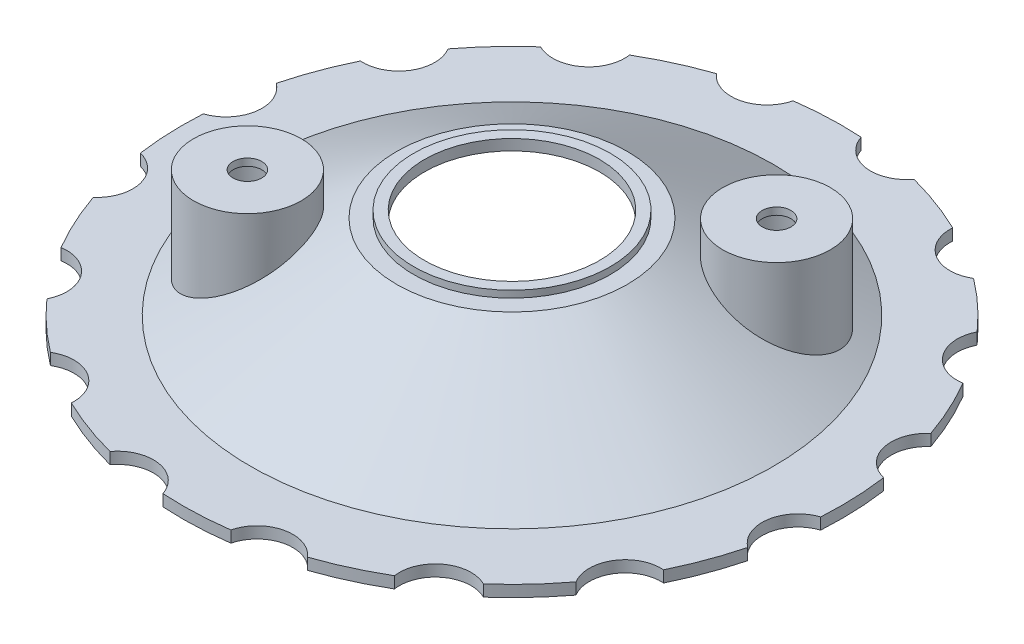
SolidWorks part; units mm, degrees
note: The reader was unsure of these and kept them because the rebuilt part matched: shared geometry of "Sketch4<6>", "Sketch3<4>", "Sketch4<8>", "Sketch4<10>", "Sketch4<11>".
ref_plane "Front Plane" through (0, 0, 0) normal (0, 0, 1) x (1, 0, 0)
ref_plane "Top Plane" through (0, 0, 0) normal (0, 1, 0) x (1, 0, 0)
ref_plane "Right Plane" through (0, 0, 0) normal (1, 0, 0) x (0, 0, -1)
sketch "Sketch3" plane through (0, 0, 0) normal (0, 0, 1) x (1, 0, 0)
  line L0 (0, 0) -> (0, 8)
  line L1 (0, 8) -> (6.1, 8)
  line L2 (6.1, 8) -> (19.9564, 0)
  line L3 (19.9564, 0) -> (6.1, 0)
  line L4 (6.1, 0) -> (0, 0)
  line L5 (19.9564, 1.3856) -> (8.0323, 8.27)
  line L6 (19.9564, 0) -> (19.9564, 1.3856)
  line L7 (6.85, 8.75) -> (6.85, 8.27)
  line L8 (6.1, 8) -> (6.1, 8.75)
  line L9 (6.1, 8.75) -> (6.85, 8.75)
  line L10 (6.85, 8.27) -> (8.0323, 8.27)
  line L11 (22.9564, 0) -> (22.9564, 2.39)
  line L12 (22.9564, 2.39) -> (15.8168, 2.39)
  line L13 (22.9564, 0) -> (19.9564, 0)
  dimension "D1" = 19.9564
  dimension "D2" = 60
  dimension "D3" = 8
  dimension "D4" = 0.75
  dimension "D5" = 0.48
  dimension "D6" = 0.75
  dimension "D7" = 6.1
  dimension "D8" = 1.2
  dimension "D9" = 2.39
  dimension "D10" = 1.3856
  dimension "D11" = 22.9564
ref_axis "Axis1" through (0, 0, 0) along (0, 1, 0)
revolve "Revolve1" add sketch "Sketch3" angle 360 about axis through (0, 0, 0) along (0, 1, 0)
sketch "Sketch4" plane through (0, 0, 0) normal (0, 1, 0) x (1, 0, 0)
  line L0 (118.8917, 681.3815) -> (968.8917, 681.3815) construction
  line L1 (-10.6926, -7.74) -> (10.6926, 7.74)
  line L5 (31.7232, 27.4788) -> (0, 0)
  line L6 (0, 0) -> (-32.7711, 26.633)
  line L7 (0.7496, -47.7541) -> (0, 0)
  line L8 (0, 0) -> (-24, -0.3767)
  line L9 (0, 0) -> (-19.4317, -14.0857)
  circle A1 centre (-32.7711, 26.633) radius 1.7004
  circle A2 centre (0.7496, -47.7541) radius 1.6902
  circle A3 centre (31.7232, 27.4788) radius 1.7049
  circle A4 centre (0, 0) radius 13.2
  circle A5 centre (0, 0) radius 19.96
  circle A6 centre (-10.6926, -7.74) radius 2.25
  circle A7 centre (10.6926, 7.74) radius 2.25
  circle A8 centre (10.6926, 7.74) radius 3.75
  circle A9 centre (-10.6926, -7.74) radius 3.75
  circle A26 centre (-19.4317, -14.0857) radius 2.5
  circle A27 centre (-23.343, -5.5773) radius 2.5
  circle A28 centre (-23.7004, 3.7802) radius 2.5
  circle A29 centre (-20.4497, 12.5622) radius 2.5
  circle A30 centre (-14.0857, 19.4317) radius 2.5
  circle A31 centre (-5.5773, 23.343) radius 2.5
  circle A32 centre (3.7802, 23.7004) radius 2.5
  circle A33 centre (12.5622, 20.4497) radius 2.5
  circle A34 centre (19.4317, 14.0857) radius 2.5
  circle A35 centre (23.343, 5.5773) radius 2.5
  circle A36 centre (23.7004, -3.7802) radius 2.5
  circle A37 centre (20.4497, -12.5622) radius 2.5
  circle A38 centre (14.0857, -19.4317) radius 2.5
  circle A39 centre (5.5773, -23.343) radius 2.5
  circle A40 centre (-3.7802, -23.7004) radius 2.5
  circle A41 centre (-12.5622, -20.4497) radius 2.5
  spline S1 degree 3 poles (43.8735, -26.7609) (31.5074, -48.7539) (7.0538, -66.6063) (-36.5969, -52.4475) (-49.7377, -17.6551) (-51.9696, 4.1899) (-49.3092, 25.911) (-32.1878, 46.9787) (-4.6171, 56.277) (26.6667, 51.503) (51.4432, 21.9878) (49.0137, -13.034) (43.8735, -26.7609) (31.5074, -48.7539) (7.0538, -66.6063) knots -0.186216 -0.081166 -0.008117 0 0.104424 0.202069 0.320062 0.340993 0.411384 0.528959 0.5813 0.689189 0.813784 0.918834 0.991883 1 1.104424 1.202069 1.320062 only from (37.8954, -37.3216) to (37.8954, -37.3216)
  point P61 (0, 0)
  dimension "D5" = 7.5
  dimension "D6" = 4.5
  dimension "D7" = 4.5
  dimension "D8" = 7.5
  dimension "D9" = 26.4
  dimension "D11" = 24
  dimension "D14" = 16
  dimension "D12" = 5
  dimension "D1" = 130
  dimension "D2" = 130
  dimension "D3" = 42.2287
  dimension "D4" = 41.9696
  dimension "D10" = 24
  dimension "D13" = 55
extrude "Boss-Extrude1" add sketch "Sketch4" along normal blind 1
extrude "Boss-Extrude2" add sketch "Sketch4<6>" along direction (0, 1, 0) on the side of the normal blind 9.2 contours L1 A9 A4 A6 | A4 A9 L1 A6 | A4 A8 L5 A7 | L5 A8 A4 A7 | A4 A8 L5 A7 | L5 A8 L1 A7 | L1 A8 A4 A7 | A4 A9 L9 A6 | L9 A9 A4 A6 | A4 A9 L9 A6
sketch "Sketch4<6>" plane through (0, 0, 0) normal (0, 1, 0) x (1, 0, 0) same geometry as "Sketch4"
revolve "Cut-Revolve1" cut sketch "Sketch3<4>" angle 360 about axis through (0, 0, 0) along (0, 1, 0)
sketch "Sketch3<4>" plane through (0, 0, 0) normal (0, 0, 1) x (1, 0, 0) same geometry as "Sketch3"
ref_plane "Plane3" through (0, 9.2, 0) normal (0, 1, 0) x (1, 0, 0)
sketch "Sketch6" plane through (0, 9.2, 0) normal (0, 1, 0) x (1, 0, 0)
  line L0 (0, 0) -> (-10.6926, -7.74)
  line L5 (0, 0) -> (10.6926, 7.74)
  circle A5 centre (-10.6926, -7.74) radius 1
  circle A6 centre (-10.6926, -7.74) radius 3.75
  circle A9 centre (10.6926, 7.74) radius 1
  circle A10 centre (10.6926, 7.74) radius 3.75
  point P7 (-0.0007, 0)
  dimension "D1" = 2
  dimension "D2" = 7.5
  dimension "D3" = 2
extrude "Boss-Extrude10" add sketch "Sketch6" along normal blind 0.5
extrude "Cut-Extrude1" cut sketch "Sketch4<8>" along normal blind 8 contours A6 | A7
sketch "Sketch4<8>" plane through (0, 0, 0) normal (0, 1, 0) x (1, 0, 0) same geometry as "Sketch4"
extrude "Cut-Extrude3" cut sketch "Sketch4<10>" along normal blind 1.59 contours S1
sketch "Sketch4<10>" plane through (0, 0, 0) normal (0, 1, 0) x (1, 0, 0) same geometry as "Sketch4"
extrude "Cut-Extrude4" cut sketch "Sketch4<11>" along normal blind 30
sketch "Sketch4<11>" plane through (0, 0, 0) normal (0, 1, 0) x (1, 0, 0) same geometry as "Sketch4"
